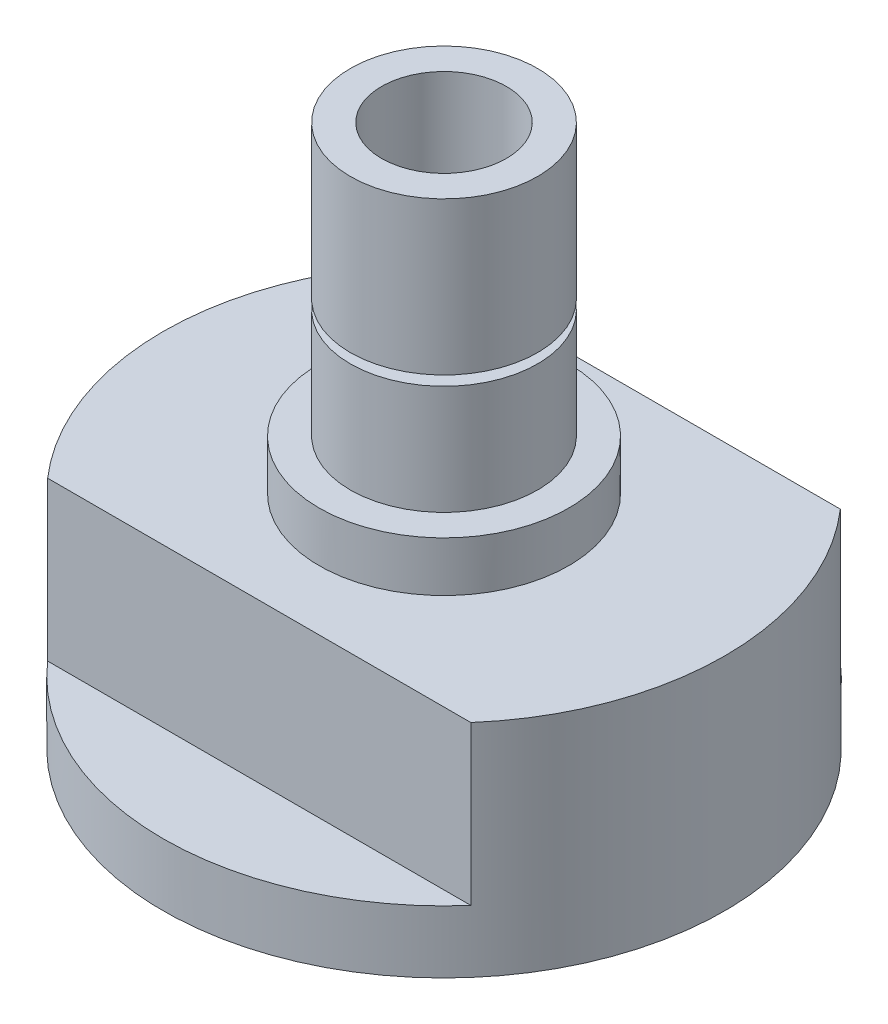
SolidWorks part; units mm, degrees
ref_plane "Front Plane" through (0, 0, 0) normal (0, 0, 1) x (1, 0, 0)
ref_plane "Top Plane" through (0, 0, 0) normal (0, 1, 0) x (1, 0, 0)
ref_plane "Right Plane" through (0, 0, 0) normal (1, 0, 0) x (0, 0, -1)
sketch "Sketch1" plane through (0, 0, 0) normal (0, 1, 0) x (1, 0, 0)
  circle A0 centre (0, 0) radius 12.7
  circle A1 centre (0, 0) radius 6.35
  dimension "D1" = 25.4
  dimension "D2" = 12.7
extrude "Boss-Extrude1" add sketch "Sketch1" along normal blind 5.08
sketch "Sketch2" plane through (0, 5.08, 0) normal (0, 1, 0) x (1, 0, 0)
  circle A0 centre (0, 0) radius 6.35
  circle A1 centre (0, 0) radius 9.525
  dimension "D1" = 19.05
  dimension "D2" = 3.175
extrude "Boss-Extrude2" add sketch "Sketch2" along normal blind 27.6225
ref_plane "Plane1" through (0, 16.1925, 0) normal (0, 1, 0) x (-1, 0, 0)
sketch "Sketch3" plane through (0, 16.1925, 0) normal (0, 1, 0) x (-1, 0, 0)
  circle A0 centre (0, 0) radius 7.4676
  dimension "D1" = 14.9352
extrude "Cut-Extrude1" cut sketch "Sketch3" along normal blind 0.9906 flip side to cut
sketch "Sketch4" plane through (0, 0, 0) normal (0, -1, 0) x (1, 0, 0)
  circle A0 centre (0, 0) radius 12.7 construction
  circle A4 centre (0, 0) radius 12.7
  circle A5 centre (0, 0) radius 15.875
  dimension "D4" = 31.75
sketch "Sketch5" plane through (0, 0, 0) normal (0, -1, 0) x (1, 0, 0)
  line L0 (-17.5, 0) -> (17.5, 0) construction
  circle A1 centre (0, 0) radius 17.5 construction
  circle A4 centre (0, 0) radius 28.575
  dimension "D2" = 35
  dimension "D4" = 57.15
extrude "Boss-Extrude4" add sketch "Sketch5" along normal blind 6.5875
sketch "Sketch8" plane through (0, -6.5875, 0) normal (0, -1, 0) x (1, 0, 0)
  line L0 (-23.7595, -15.875) -> (23.7595, -15.875)
  line L1 (-23.7595, 15.875) -> (23.7595, 15.875)
  line L2 (-23.7595, -15.875) -> (-23.7595, 15.875) construction
  line L3 (23.7595, -15.875) -> (23.7595, 15.875) construction
  circle A0 centre (0, 0) radius 28.575 construction
  circle M3 centre (0, 0) radius 28.575
  dimension "D1" = 31.75
extrude "Boss-Extrude5" add sketch "Sketch8" along normal blind 15.875 contours L0 M3 | L1 M3 region at (0, -6.5875, -21.0662) region at (0, -6.5875, 21.0662)
ref_plane "Plane2" through (0, -22.4625, 0) normal (0, -1, 0) x (-1, 0, 0)
ref_axis "Axis1" through (0, 32.7025, 0) along (0, -1, 0)
sketch "Sketch11" plane through (0, 0, -15.875) normal (0, 0, 1) x (1, 0, 0)
  line L0 (3.175, -22.4625) -> (3.175, -9.7625)
  line L1 (-23.7595, -22.4625) -> (23.7595, -22.4625) construction
  line L2 (-23.7595, -6.5875) -> (23.7595, -6.5875) construction
  line L3 (-3.175, -22.4625) -> (-3.175, -9.7625)
  line L4 (3.175, -22.4625) -> (23.7595, -22.4625) construction
  line L5 (-3.175, -22.4625) -> (-23.7595, -22.4625) construction
  line L6 (23.7595, -22.4625) -> (23.7595, -6.5875) construction
  line L7 (-23.7595, -22.4625) -> (-23.7595, -6.5875) construction
  arc A0 (3.175, -9.7625) -> (-3.175, -9.7625) centre (0, -9.7625) ccw
  dimension "D1" = 6.35
sketch "Sketch12" plane through (0, 0, 0) normal (0, 1, 0) x (1, 0, 0)
  line L1 (-28.575, 18.796) -> (28.575, 18.796)
  line L2 (-28.575, 18.796) -> (-28.575, 28.575)
  line L3 (-28.575, 28.575) -> (28.575, 28.575)
  line L4 (28.575, 18.796) -> (28.575, 28.575)
  line L5 (28.575, -28.575) -> (-28.575, -28.575)
  line L6 (28.575, -28.575) -> (28.575, -18.796)
  line L7 (28.575, -18.796) -> (-28.575, -18.796)
  line L8 (-28.575, -28.575) -> (-28.575, -18.796)
  circle A0 centre (0, 0) radius 28.575 construction
  dimension "D1" = 9.779
  dimension "D2" = 9.779
extrude "Cut-Extrude2" cut sketch "Sketch12" against normal offset from surface (16.1125 mm away) 6.35 up to face at (0, -22.4625, 22.225)
sketch "Sketch13" plane through (0, -6.5875, 0) normal (0, -1, 0) x (1, 0, 0)
  line L2 (23.7595, 15.875) -> (-23.7595, 15.875)
  line L3 (-23.7595, -15.875) -> (23.7595, -15.875)
  line L4 (23.7595, 15.875) -> (-23.7595, 15.875)
  line L5 (-23.7595, -15.875) -> (23.7595, -15.875)
  arc A2 (23.7595, -15.875) -> (23.7595, 15.875) centre (0, 0) ccw
  arc A3 (-23.7595, 15.875) -> (-23.7595, -15.875) centre (0, 0) ccw
  arc A4 (23.7595, -15.875) -> (23.7595, 15.875) centre (0, 0) ccw
  arc A5 (-23.7595, 15.875) -> (-23.7595, -15.875) centre (0, 0) ccw
  dimension "D1" = 0
extrude "Boss-Extrude6" add sketch "Sketch13" along normal up to surface (15.875 mm away) up to face at (0, -22.4625, -22.225)
